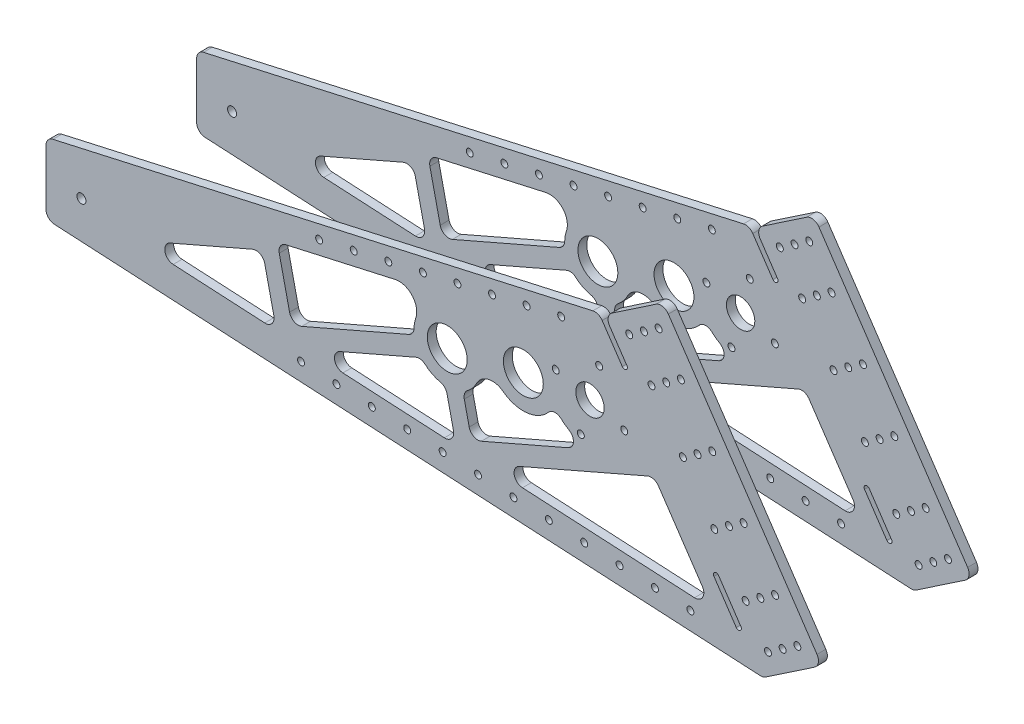
SolidWorks part; units mm, degrees
other "Markup1"
sketch "Sketch2"
sketch "Sketch9" plane through (0, 0, 0) normal (0, 0, 1) x (1, 0, 0)
sketch "Sketch12" plane through (116.0373, 167.646, 63.5) normal (0, 0, 1) x (1, 0, 0)
sketch "Sketch13" plane through (116.0373, 167.646, 63.5) normal (0, 0, 1) x (1, 0, 0)
sketch "Sketch14" plane through (116.0373, 167.646, 63.5) normal (0, 0, 1) x (1, 0, 0)
sketch "Sketch16" plane through (116.0373, 167.646, 63.5) normal (0, 0, 1) x (1, 0, 0)
sketch "Sketch17" plane through (116.0373, 167.8557, 63.5) normal (0, 0, 1) x (1, 0, 0)
sketch "Sketch18" plane through (116.0373, 167.7906, 57.15) normal (0, 0, 1) x (1, 0, 0)
sketch "Sketch19" plane through (84.5137, 127.089, 57.15) normal (0, 0, 1) x (1, 0, 0)
material "6061-T6 (SS)"
ref_plane "Front Plane" through (0, 0, 0) normal (0, 0, 1) x (1, 0, 0)
ref_plane "Top Plane" through (0, 0, 0) normal (0, 1, 0) x (1, 0, 0)
ref_plane "Right Plane" through (0, 0, 0) normal (1, 0, 0) x (0, 0, -1)
sketch "Grid" plane through (0, 0, 0) normal (0, 0, 1) x (1, 0, 0)
  line L0 (-23.2766, 0) -> (153.3593, 0) construction
  line L1 (0, 0) -> (0, 151.4205) construction
  line L6 (-1009.65, 1168.4) -> (-1009.65, 0) construction
  line L15 (-361.95, 520.7) -> (-803.275, 520.7)
  line L16 (-361.95, 520.7) -> (-361.95, 0)
  line L17 (-361.95, 0) -> (-803.275, 0)
  line L18 (-803.275, 520.7) -> (-803.275, 0)
  line L19 (-803.275, 0) -> (-1244.6, 0)
  line L20 (-803.275, 0) -> (-803.275, 825.5)
  line L21 (-803.275, 825.5) -> (-1244.6, 825.5)
  line L22 (-1244.6, 0) -> (-1244.6, 825.5)
  line L23 (-1030.732, 0) -> (-988.568, 0)
  line L24 (-1030.732, 0) -> (-1030.732, 1168.4)
  line L25 (-1030.732, 1168.4) -> (-988.568, 1168.4)
  line L26 (-988.568, 0) -> (-988.568, 1168.4)
  line L27 (-598.932, 0) -> (-556.768, 0)
  line L28 (-598.932, 0) -> (-598.932, 863.6)
  line L29 (-598.932, 863.6) -> (-556.768, 863.6)
  line L30 (-556.768, 0) -> (-556.768, 863.6)
  line L31 (-577.85, 863.6) -> (-577.85, 0) construction
  line L32 (-361.95, 520.7) -> (-361.95, 596.9) construction
  line L33 (-803.275, 825.5) -> (-803.275, 901.7) construction
  line L34 (-370.0766, 0) -> (-263.7141, 304.8)
  line L35 (-263.7141, 304.8) -> (-157.3516, 0)
  line L36 (-157.3516, 0) -> (-370.0766, 0)
  circle A0 centre (-100.3958, 159.9664) radius 120.65
  dimension "D3" = 241.3
  dimension "D2" = 76.2
  dimension "D4" = 304.8
  dimension "D5" = 212.725
  dimension "D7" = 42.164
  dimension "D8" = 520.7
  dimension "D9" = 304.8
  dimension "D10" = 1168.4
  dimension "D11" = 863.6
  dimension "D12" = 361.95
  dimension "D13" = 577.85
  dimension "D14" = 803.275
  dimension "D15" = 1009.65
sketch "ChassisXY" plane through (0, 0, 0) normal (0, 0, 1) x (1, 0, 0)
  line L0 (755.65, 93.726) -> (95.25, 93.726)
  line L1 (755.65, 93.726) -> (755.65, 42.926)
  line L2 (755.65, 42.926) -> (95.25, 42.926)
  line L3 (95.25, 93.726) -> (95.25, 42.926)
  line L15 (736.7108, 119.126) -> (675.4349, 119.126)
  line L16 (787.4, 42.926) -> (768.35, 42.926)
  line L19 (63.5, 169.926) -> (82.55, 169.926)
  line L20 (736.7108, 119.126) -> (694.5957, 90.719) construction
  line L21 (736.7108, 119.126) -> (717.55, 147.533) construction
  line L22 (694.5957, 90.719) -> (675.4349, 119.126) construction
  line L23 (717.55, 147.533) -> (675.4349, 119.126) construction
  line L27 (63.5, 169.926) -> (63.5, 42.926)
  line L31 (88.9, 42.926) -> (88.9, 1979.9925) construction
  line L32 (62.806, 1979.9925) -> (762, 1979.9925) construction
  line L33 (63.5, 42.926) -> (82.55, 42.926)
  line L36 (88.9, 1320.8) -> (762, 1320.8) construction
  line L37 (88.9, 988.6997) -> (131.0151, 1017.1067) construction
  line L45 (63.5, 42.926) -> (31.75, 42.926)
  line L46 (717.55, 147.533) -> (675.4349, 119.126) construction
  line L47 (717.55, 147.533) -> (-518.4596, 1979.9925) construction
  line L48 (675.4349, 119.126) -> (-560.5747, 1951.5855) construction
  line L49 (-518.4596, 1979.9925) -> (-560.5747, 1951.5855) construction
  line L50 (63.5, 42.926) -> (63.5, 169.926)
  line L51 (0, 74.676) -> (0, 138.176)
  line L52 (31.75, 169.926) -> (63.5, 169.926)
  line L54 (425.45, 93.726) -> (425.45, 42.926) construction
  line L55 (762, 42.926) -> (762, 1979.9925) construction
  line L56 (819.15, 169.926) -> (787.4, 169.926)
  line L57 (850.9, 74.676) -> (850.9, 138.176)
  line L58 (787.4, 42.926) -> (787.4, 169.926)
  line L59 (787.4, 42.926) -> (819.15, 42.926)
  line L60 (82.55, 169.926) -> (82.55, 42.926)
  line L61 (768.35, 169.926) -> (768.35, 42.926)
  line L62 (787.4, 169.926) -> (768.35, 169.926)
  line L63 (787.4, 169.926) -> (787.4, 42.926)
  line L64 (0, 0) -> (0, 200151.4205) construction
  line L65 (-200023.2766, 0) -> (200153.3593, 0) construction
  line L66 (95.25, 152.4) -> (755.65, 152.4) construction
  arc A5 (31.75, 169.926) -> (0, 138.176) centre (31.75, 138.176) ccw
  arc A6 (0, 74.676) -> (31.75, 42.926) centre (31.75, 74.676) ccw
  circle A7 centre (31.75, 74.676) radius 31.75 construction
  circle A8 centre (31.75, 138.176) radius 31.75 construction
  circle A9 centre (819.15, 138.176) radius 31.75 construction
  circle A10 centre (819.15, 74.676) radius 31.75 construction
  arc A11 (850.9, 74.676) -> (819.15, 42.926) centre (819.15, 74.676) cw
  arc A12 (819.15, 169.926) -> (850.9, 138.176) centre (819.15, 138.176) cw
  dimension "D3" = 63.5
  dimension "D1" = 50.8
  dimension "D2" = 56
  dimension "D4" = 38.1
  dimension "D5" = 50.8
  dimension "D6" = 12.7
  dimension "D7" = 19.05
  dimension "D8" = 42.926
  dimension "D9" = 109.474
  dimension "D10" = 25.4
  dimension "D12" = 660.4
  dimension "D13" = 6.35
ref_plane "Plane1" through (561.5696, 378.7835, 0) normal (0.829, 0.5592, 0) x (-0.5592, 0.829, 0)
sketch "carriage geo" plane through (0, 0, 0) normal (0, 0, 1) x (1, 0, 0)
  line L1 (116.0373, 195.326) -> (624.0373, 195.326)
  line L2 (116.0373, 195.326) -> (116.0373, 246.126)
  line L3 (116.0373, 246.126) -> (624.0373, 246.126)
  line L4 (624.0373, 195.326) -> (624.0373, 246.126)
  line L6 (624.0373, 195.326) -> (700.6322, 195.326) construction
  line L17 (717.55, 147.533) -> (-518.4596, 1979.9925) construction
  line L24 (624.0373, 246.126) -> (666.3671, 246.126) construction
  line L33 (666.3671, 246.126) -> (700.6322, 195.326) construction
  line L35 (675.4349, 119.126) -> (-560.5747, 1951.5855) construction
  line L64 (755.65, 93.726) -> (95.25, 93.726) construction
  circle A0 centre (154.1373, 220.726) radius 14.2875
  circle A58 centre (256.8816, 507.741) radius 25.4
  line B0 (120.4355, 364.2548) -> (144.4436, 355.656) construction
  line B1 (345.3934, 565.2279) -> (248.3868, 535.0242)
  line B2 (339.9907, 375.4447) -> (343.9447, 374.0285) construction
  line B3 (348.2442, 386.0326) -> (300.3235, 403.196) construction
  line B4 (308.577, 413.7839) -> (348.5895, 399.4529)
  line B5 (107.1432, 327.1426) -> (206.8255, 291.4401)
  line B6 (112.3162, 360.4178) -> (103.3062, 335.2619)
  line B7 (352.5436, 398.0367) -> (348.5895, 399.4529) construction
  line B8 (366.599, 439.1494) -> (341.413, 442.4393) construction
  line B9 (353.8882, 537.9448) -> (341.413, 442.4393) construction
  line B10 (343.9447, 374.0285) -> (352.5436, 398.0367)
  line B11 (348.5895, 399.4529) -> (308.577, 413.7839)
  line B12 (304.6229, 415.2001) -> (296.0241, 391.1919)
  line B13 (299.9781, 389.7757) -> (339.9907, 375.4447)
  line B14 (140.4752, 344.576) -> (141.8914, 348.5301) construction
  line B15 (129.3385, 325.9381) -> (133.2925, 324.5219) construction
  line B16 (110.7006, 337.0748) -> (109.2844, 333.1207) construction
  line B17 (121.8372, 355.7127) -> (117.8832, 357.1289) construction
  line B18 (117.8832, 357.1289) -> (110.7006, 337.0748)
  line B19 (109.2844, 333.1207) -> (129.3385, 325.9381)
  line B20 (141.8914, 348.5301) -> (121.8372, 355.7127)
  line B21 (133.2925, 324.5219) -> (140.4752, 344.576)
  line B22 (296.0241, 391.1919) -> (299.9781, 389.7757) construction
  line B23 (308.577, 413.7839) -> (304.6229, 415.2001) construction
  arc B24 (248.3868, 535.0242) -> (233.4586, 491.3735) centre (256.8816, 507.741) ccw
  circle B25 centre (256.8816, 507.741) radius 3.1877
  circle B26 centre (353.8882, 537.9448) radius 3.1877
  arc B27 (107.1432, 327.1426) -> (103.3062, 335.2619) centre (109.2844, 333.1207) cw
  circle B28 centre (341.413, 442.4393) radius 30 construction
  arc B29 (121.2422, 363.9009) -> (112.3162, 360.4178) centre (118.2943, 358.2767) ccw
  arc B30 (233.4586, 491.3735) -> (121.2422, 363.9009) centre (161.817, 441.3116) cw
  circle B31 centre (341.413, 442.4393) radius 25.4 construction
  circle B32 centre (366.599, 439.1494) radius 2.4892
  circle B33 centre (338.1231, 417.2533) radius 2.4892
  circle B34 centre (316.2269, 445.7292) radius 2.4892
  circle B35 centre (344.7029, 467.6254) radius 2.4892
  circle B36 centre (341.413, 442.4393) radius 10.16
  circle B37 centre (147.3899, 326.2177) radius 2.4892
  arc B38 (376.4624, 520.4251) -> (367.6342, 457.9958) centre (426.6271, 481.4924) ccw
  arc B39 (367.6342, 457.9958) -> (206.8255, 291.4401) centre (249.6484, 411.0026) cw
  arc B40 (133.2925, 324.5219) -> (129.3385, 325.9381) centre (131.3155, 325.23) cw
  arc B41 (343.9447, 374.0285) -> (339.9907, 375.4447) centre (341.9677, 374.7366) cw
  arc B42 (296.0241, 391.1919) -> (299.9781, 389.7757) centre (298.0011, 390.4838) ccw
  arc B43 (352.5436, 398.0367) -> (348.5895, 399.4529) centre (350.5666, 398.7448) ccw
  arc B44 (304.6229, 415.2001) -> (308.577, 413.7839) centre (306.5999, 414.492) cw
  arc B45 (109.2844, 333.1207) -> (110.7006, 337.0748) centre (109.9925, 335.0977) cw
  arc B46 (117.8832, 357.1289) -> (121.8372, 355.7127) centre (119.8602, 356.4208) cw
  arc B47 (141.8914, 348.5301) -> (140.4752, 344.576) centre (141.1833, 346.553) cw
  circle B48 centre (353.8882, 537.9448) radius 28.575
  line B49 (343.9447, 374.0285) -> (296.1197, 391.1577)
  line B50 (343.9447, 374.0285) -> (318.251, 302.291)
  line B51 (296.1197, 391.1577) -> (270.426, 319.4201)
  line B52 (318.251, 302.291) -> (270.426, 319.4201) construction
  line B53 (141.8571, 348.4344) -> (133.2925, 324.5219) construction
  line B54 (165.7696, 339.8698) -> (237.5071, 314.1761)
  line B55 (157.205, 315.9573) -> (228.9426, 290.2636)
  line B56 (237.5071, 314.1761) -> (228.9426, 290.2636) construction
  line B57 (161.4873, 327.9136) -> (233.2249, 302.2198) construction
  line B58 (165.7696, 339.8698) -> (157.205, 315.9573)
  line B59 (133.2925, 324.5219) -> (157.205, 315.9573) construction
  line B60 (141.8571, 348.4344) -> (165.7696, 339.8698) construction
  line B61 (308.4359, 312.5514) -> (331.9885, 378.3108) construction
  line B62 (320.0322, 382.5931) -> (294.3385, 310.8556) construction
  arc B63 (155.075, 274.6929) -> (165.7608, 168.0174) centre (154.1373, 220.726) ccw
  circle B64 centre (176.5553, 212.6967) radius 2.4892
  circle B65 centre (158.3928, 197.2968) radius 2.4892
  circle B66 centre (135.9748, 205.3261) radius 2.4892
  circle B67 centre (131.7194, 228.7553) radius 2.4892
  circle B68 centre (149.8819, 244.1552) radius 2.4892
  circle B69 centre (172.2999, 236.1259) radius 2.4892
  circle B70 centre (154.1373, 220.726) radius 23.8125 construction
  circle B71 centre (308.4359, 312.5514) radius 2.4892
  arc B72 (165.7608, 168.0174) -> (155.075, 274.6929) centre (154.1373, 220.726) ccw construction
  circle B73 centre (227.2467, 304.361) radius 2.4892
  circle B74 centre (284.5234, 321.116) radius 2.4892
  arc B75 (290.7123, 376.06) -> (193.2811, 330.0162) centre (218.9748, 401.7538) cw
  arc B76 (318.251, 302.291) -> (165.7608, 168.0174) centre (120.5341, 373.1059) cw
  circle B77 centre (312.7182, 324.5077) radius 2.4892
  circle B78 centre (288.8057, 333.0722) radius 2.4892
  circle B79 centre (317.0005, 336.4639) radius 2.4892
  circle B80 centre (293.088, 345.0285) radius 2.4892
  circle B81 centre (321.2828, 348.4202) radius 2.4892
  circle B82 centre (297.3703, 356.9847) radius 2.4892
  circle B83 centre (325.5651, 360.3764) radius 2.4892
  circle B84 centre (301.6526, 368.941) radius 2.4892
  circle B85 centre (329.8473, 372.3327) radius 2.4892
  circle B86 centre (305.9348, 380.8972) radius 2.4892
  arc B87 (162.2796, 314.1398) -> (155.075, 274.6929) centre (155.4279, 295.0098) cw
  circle B88 centre (215.2905, 308.6433) radius 2.4892
  circle B89 centre (203.3342, 312.9256) radius 2.4892
  circle B90 centre (191.378, 317.2079) radius 2.4892
  circle B91 centre (179.4217, 321.4901) radius 2.4892
  circle B92 centre (167.4655, 325.7724) radius 2.4892
  dimension "D2" = 28.575
  dimension "D3" = 25.4
  dimension "D4" = 38.1
  dimension "D8" = 101.6
  dimension "D5" = 50.8
  dimension "D1" = 50.8
  dimension "D6" = 12.7
  dimension "D7" = 508
sketch_block_instance "Block25-1"
sketch_block "Block25"
sketch_block_instance "Block26-1"
sketch_block "Block26"
sketch "carrriageyz" plane through (561.5696, 378.7835, 0) normal (0.829, 0.5592, 0) x (-0.5592, 0.829, 0)
  line L0 (-313.2035, 69.85) -> (769.957, 69.85) construction
  line L1 (769.957, -69.85) -> (-313.2035, -69.85) construction
  line L2 (-262.4035, 69.85) -> (-262.4035, -69.85) construction
  line L4 (-313.2035, 69.85) -> (-313.2035, -69.85) construction
  line L5 (-313.2035, 0) -> (-278.9385, 0) construction
  line L6 (769.957, 69.85) -> (769.957, -69.85) construction
  line L7 (-249.7114, 57.15) -> (-249.7114, 50.8)
  line L8 (-249.7114, 57.15) -> (-97.3114, 57.15)
  line L9 (-249.7114, 50.8) -> (-97.3114, 50.8)
  line L10 (-97.3114, 57.15) -> (-97.3114, 50.8)
  line L11 (106.8647, 0) -> (-106.8647, 0) construction
  line L12 (-97.3114, -57.15) -> (-97.3114, -50.8)
  line L13 (-249.7114, -50.8) -> (-97.3114, -50.8)
  line L14 (-249.7114, -57.15) -> (-97.3114, -57.15)
  line L15 (-249.7114, -57.15) -> (-249.7114, -50.8)
  line L16 (-218.5469, 31.75) -> (-148.6639, 31.75)
  line L17 (-174.4547, 57.15) -> (-206.8488, 57.15)
  line L19 (-221.2897, -57.15) -> (-160.0138, -57.15)
  line L21 (-219.5489, -57.15) -> (-127.4739, -57.15)
  line L22 (-219.5489, 63.5) -> (-127.4739, 63.5)
  line L23 (-219.5489, 63.5) -> (-219.5489, 57.15)
  line L24 (-219.5489, 57.15) -> (-127.4739, 57.15)
  line L25 (-127.4739, 63.5) -> (-127.4739, 57.15)
  line L26 (-127.4739, -63.5) -> (-127.4739, -57.15)
  line L27 (-219.5489, -63.5) -> (-127.4739, -63.5)
  line L28 (-219.5489, -63.5) -> (-219.5489, -57.15)
  line L29 (-218.5469, 31.75) -> (-218.5469, -31.75)
  line L30 (-218.5469, -31.75) -> (-148.6639, -31.75)
  line L31 (-148.6639, 31.75) -> (-148.6639, -31.75)
  line L33 (-97.3114, -69.1134) -> (-125.8864, -69.1134)
  line L34 (-97.3114, 57.15) -> (-125.8864, 57.15)
  line L35 (-97.3114, 57.15) -> (-97.3114, 69.1134)
  line L36 (-97.3114, 69.1134) -> (-125.8864, 69.1134)
  line L37 (-125.8864, 57.15) -> (-125.8864, 69.1134)
  line L38 (-249.7114, 57.15) -> (-221.1364, 57.15)
  line L39 (-249.7114, 57.15) -> (-249.7114, 69.1134)
  line L40 (-249.7114, 69.1134) -> (-221.1364, 69.1134)
  line L41 (-221.1364, 57.15) -> (-221.1364, 69.1134)
  line L42 (-125.8864, -57.15) -> (-125.8864, -69.1134)
  line L43 (-97.3114, -57.15) -> (-125.8864, -57.15)
  line L44 (-97.3114, -57.15) -> (-97.3114, -69.1134)
  line L45 (-249.7114, -69.1134) -> (-221.1364, -69.1134)
  line L46 (-221.1364, -57.15) -> (-221.1364, -69.1134)
  line L47 (-249.7114, -57.15) -> (-221.1364, -57.15)
  line L48 (-249.7114, -57.15) -> (-249.7114, -69.1134)
  line L49 (-111.5989, 69.1134) -> (-111.5989, -69.1134) construction
  line L50 (-235.4239, 69.1134) -> (-235.4239, -69.1134) construction
  point P4 (-313.2035, 0)
  point P31 (-148.6639, 0)
  point P41 (-190.6518, 57.15)
  point P53 (-111.5989, 0)
  dimension "D1" = 139.7
  dimension "D2" = 12.7
  dimension "D3" = 6.35
  dimension "D4" = 63.5
  dimension "D5" = 6.35
  dimension "D6" = 152.4
  dimension "D7" = 28.575
  dimension "D8" = 11.9634
  dimension "D9" = 50.8
  dimension "D10" = 1.5875
  dimension "D11" = 1.5875
ref_plane "bearing block interface plane" through (0, 0, 57.15) normal (0, 0, 1) x (1, 0, 0)
sketch "bearing block interface plate" plane through (0, 0, 57.15) normal (0, 0, 1) x (1, 0, 0)
  line L0 (529.0514, 336.1484) -> (571.1665, 364.5554)
  line L1 (529.0514, 336.1484) -> (642.6794, 167.688)
  line L2 (571.1665, 364.5554) -> (684.7945, 196.095)
  line L3 (642.6794, 167.688) -> (684.7945, 196.095)
  line L4 (675.4349, 119.126) -> (-560.5747, 1951.5855) construction
  line L5 (717.55, 147.533) -> (-518.4596, 1979.9925) construction
  line L6 (635.5777, 178.2167) -> (677.6928, 206.6237) construction
  line L7 (585.8654, 251.9182) -> (627.9805, 280.3252) construction
  line L10 (545.0304, 312.4586) -> (587.1455, 340.8656) construction
  line L12 (528.3092, 320.3288) -> (546.682, 332.7214) construction
  line L15 (606.2073, 289.894) -> (628.6962, 256.5529) construction
  line L16 (522.4272, 322.7212) -> (526.7202, 333.2764) construction
  line L17 (529.0514, 336.1484) -> (536.1532, 325.6196) construction
  line L18 (527.0768, 314.0996) -> (540.247, 311.4938) construction
  line L21 (577.876, 263.7631) -> (619.9911, 292.1701) construction
  line L22 (626.7005, 191.3777) -> (668.8156, 219.7847) construction
  line L23 (611.7695, 190.2657) -> (623.1643, 190.2921) construction
  line L24 (610.7216, 215.0675) -> (652.8367, 243.4745) construction
  line L25 (605.5175, 197.8065) -> (608.0351, 210.9939) construction
  line L26 (611.7548, 196.6157) -> (630.1275, 209.0082) construction
  circle A0 centre (646.1065, 185.3185) radius 2.4892
  circle A1 centre (656.6352, 192.4202) radius 2.4892
  circle A2 centre (667.164, 199.522) radius 2.4892
  circle A3 centre (567.7395, 346.9249) radius 2.4892
  circle A4 centre (557.2107, 339.8231) radius 2.4892
  circle A5 centre (546.682, 332.7214) radius 2.4892
  arc A7 (522.4272, 322.7212) -> (527.0768, 314.0996) centre (528.3092, 320.3288) ccw construction
  circle A12 centre (562.6609, 309.0316) radius 2.4892
  circle A13 centre (573.1897, 316.1334) radius 2.4892
  circle A14 centre (583.7185, 323.2351) radius 2.4892
  circle A15 centre (606.2073, 289.894) radius 2.4892
  circle A16 centre (595.6786, 282.7922) radius 2.4892
  circle A17 centre (585.1498, 275.6905) radius 2.4892
  circle A18 centre (628.6962, 256.5529) radius 2.4892
  circle A19 centre (618.1674, 249.4511) radius 2.4892
  circle A20 centre (607.6387, 242.3494) radius 2.4892
  circle A21 centre (651.1851, 223.2117) radius 2.4892
  circle A22 centre (640.6563, 216.11) radius 2.4892
  circle A23 centre (630.1275, 209.0082) radius 2.4892
  arc A24 (526.7202, 333.2764) -> (529.0514, 336.1484) centre (532.6023, 330.884) cw construction
  arc A25 (540.247, 311.4938) -> (545.0304, 312.4586) centre (541.4795, 317.723) ccw construction
  arc A29 (623.1643, 190.2921) -> (626.7005, 191.3777) centre (623.1496, 196.6421) ccw construction
  arc A30 (611.7695, 190.2657) -> (605.5175, 197.8065) centre (611.7548, 196.6157) cw construction
  arc A31 (608.0351, 210.9939) -> (610.7216, 215.0675) centre (614.2724, 209.8031) cw construction
  point P28 (617.4518, 273.2234)
  dimension "D3" = 4.9784
  dimension "D8" = 12.7
  dimension "D10" = 2
  dimension "D13" = 6.35
  dimension "D1" = 12.7
  dimension "D2" = 12.7
  dimension "D4" = 12.7
  dimension "D5" = 28.575
  dimension "D6" = 203.2
  dimension "D7" = 33.3375
  dimension "D9" = 9.4615
  dimension "D11" = 4
  dimension "D12" = 12.7
extrude "Boss-Extrude1" add sketch "bearing block interface plate" against normal blind 6.35
fillet "Fillet2" radius 6.35 4 edges at (642.6794, 167.688, 53.975) (571.1665, 364.5554, 53.975) (529.0514, 336.1484, 53.975) (684.7945, 196.095, 53.975)
ref_plane "carriage support plane" through (0, 0, 57.15) normal (0, 0, 1) x (1, 0, 0)
sketch "plate+gb" plane through (0, 0, 57.15) normal (0, 0, 1) x (1, 0, 0)
  line L1 (717.55, 147.533) -> (-518.4596, 1979.9925) construction
  line L3 (116.0373, 195.326) -> (624.0373, 195.326) construction
  line L4 (128.7373, 195.326) -> (642.6794, 167.688)
  line L8 (532.6023, 330.884) -> (639.1286, 172.9523) construction
  line L10 (116.0373, 246.126) -> (624.0373, 246.126) construction
  line L11 (128.7373, 246.126) -> (128.7373, 195.326)
  line L12 (116.0373, 195.326) -> (116.0373, 246.126) construction
  line L13 (571.1665, 364.5554) -> (529.0514, 336.1484)
  line L17 (526.5201, 336.3247) -> (543.3723, 311.3403) construction
  line L18 (528.1782, 337.4431) -> (545.0304, 312.4586)
  line L19 (416.2866, 258.7212) -> (154.1373, 220.726) construction
  line L20 (416.2683, 274.9957) -> (154.0767, 274.701) construction
  line L21 (420.8895, 243.1112) -> (169.4032, 168.9548) construction
  line L22 (518.57, 277.876) -> (525.144, 302.4105) construction
  line L24 (529.0514, 336.1484) -> (128.7373, 246.126)
  line L26 (256.3165, 274.8159) -> (529.0514, 336.1484) construction
  line L30 (524.862, 335.2063) -> (541.7142, 310.2219)
  line L31 (529.0514, 336.1484) -> (642.6794, 167.688) construction
  line L38 (642.6794, 167.688) -> (684.7945, 196.095) construction
  line L39 (642.6794, 167.688) -> (684.7945, 196.095)
  line L40 (545.0304, 312.4586) -> (587.1455, 340.8656) construction
  line L43 (609.0635, 213.9491) -> (625.0424, 190.2593) construction
  line L44 (610.7216, 215.0675) -> (626.7005, 191.3777)
  line L45 (607.4054, 212.8307) -> (623.3843, 189.1409)
  line L59 (684.7945, 196.095) -> (571.1665, 364.5554)
  circle A0 centre (470.8051, 270.9813) radius 14.2875
  circle A1 centre (416.2866, 258.7212) radius 14.2875
  arc A2 (155.075, 274.6929) -> (165.7608, 168.0174) centre (154.1373, 220.726) ccw construction
  arc A4 (165.7608, 168.0174) -> (155.075, 274.6929) centre (154.1373, 220.726) ccw construction
  circle A5 centre (518.57, 277.876) radius 10.16
  circle A12 centre (518.57, 277.876) radius 25.4 construction
  circle A13 centre (518.57, 277.876) radius 7.62 construction
  circle A14 centre (470.8051, 270.9813) radius 40.64 construction
  circle A15 centre (470.8051, 270.9813) radius 15.24 construction
  circle A16 centre (416.2866, 258.7212) radius 40.64 construction
  circle A17 centre (416.2866, 258.7212) radius 16.2745 construction
  circle A18 centre (525.144, 302.4105) radius 2.4892
  circle A19 centre (543.1045, 271.302) radius 2.4892
  circle A20 centre (511.996, 253.3415) radius 2.4892
  circle A21 centre (494.0355, 284.45) radius 2.4892
  arc A22 (528.1782, 337.4431) -> (524.862, 335.2063) centre (526.5201, 336.3247) ccw
  arc A23 (541.7142, 310.2219) -> (545.0304, 312.4586) centre (543.3723, 311.3403) ccw
  arc A24 (610.7216, 215.0675) -> (607.4054, 212.8307) centre (609.0635, 213.9491) ccw
  circle A25 centre (607.6387, 242.3494) radius 2.4892 construction
  circle A26 centre (618.1674, 249.4511) radius 2.4892 construction
  circle A27 centre (628.6962, 256.5529) radius 2.4892 construction
  circle A28 centre (606.2073, 289.894) radius 2.4892 construction
  circle A29 centre (595.6786, 282.7922) radius 2.4892 construction
  circle A30 centre (585.1498, 275.6905) radius 2.4892 construction
  circle A31 centre (562.6609, 309.0316) radius 2.4892 construction
  circle A32 centre (573.1897, 316.1334) radius 2.4892 construction
  circle A33 centre (583.7185, 323.2351) radius 2.4892 construction
  circle A35 centre (518.57, 277.876) radius 30 construction
  circle A41 centre (607.6387, 242.3494) radius 2.4892
  circle A42 centre (618.1674, 249.4511) radius 2.4892
  circle A43 centre (628.6962, 256.5529) radius 2.4892
  circle A44 centre (606.2073, 289.894) radius 2.4892
  circle A45 centre (595.6786, 282.7922) radius 2.4892
  circle A46 centre (585.1498, 275.6905) radius 2.4892
  circle A47 centre (562.6609, 309.0316) radius 2.4892
  circle A48 centre (573.1897, 316.1334) radius 2.4892
  circle A49 centre (583.7185, 323.2351) radius 2.4892
  arc A59 (623.3843, 189.1409) -> (626.7005, 191.3777) centre (625.0424, 190.2593) ccw
  circle A63 centre (567.7395, 346.9249) radius 2.4892 construction
  circle A68 centre (557.2107, 339.8231) radius 2.4892 construction
  circle A74 centre (546.682, 332.7214) radius 2.4892 construction
  circle A75 centre (651.1851, 223.2117) radius 2.4892 construction
  circle A77 centre (640.6563, 216.11) radius 2.4892 construction
  circle A78 centre (630.1275, 209.0082) radius 2.4892 construction
  circle A79 centre (567.7395, 346.9249) radius 2.4892
  circle A80 centre (557.2107, 339.8231) radius 2.4892
  circle A81 centre (546.682, 332.7214) radius 2.4892
  circle A82 centre (651.1851, 223.2117) radius 2.4892
  circle A83 centre (640.6563, 216.11) radius 2.4892
  circle A84 centre (630.1275, 209.0082) radius 2.4892
  circle A85 centre (646.1065, 185.3185) radius 2.4892 construction
  circle A86 centre (656.6352, 192.4202) radius 2.4892 construction
  circle A87 centre (667.164, 199.522) radius 2.4892 construction
  circle A91 centre (646.1065, 185.3185) radius 2.4892
  circle A93 centre (656.6352, 192.4202) radius 2.4892
  circle A94 centre (667.164, 199.522) radius 2.4892
  point P10 (534.9462, 323.8325)
  point P47 (617.053, 202.1042)
  point P64 (518.57, 277.876)
  dimension "D2" = 50.8
  dimension "D15" = 28.575
  dimension "D16" = 20.32
  dimension "D18" = 4.9784
  dimension "D19" = 15
  dimension "D20" = 31.75
  dimension "D11" = 4
  dimension "D8" = 41.275
  dimension "D9" = 50.8
  dimension "D10" = 50.8
  dimension "D12" = 12.7
  dimension "D17" = 4
extrude "Boss-Extrude2" add sketch "plate+gb" against normal blind 6.35 contours L13 L11 L4 A49 A48 A47 A46 A45 A44 A43 A42 A41 A94 A93 A91 A21 A20 A19 A18 A5 A1 region at (431.8967, 241.8923, 57.15)
fillet "Fillet1" radius 6.35 7 edges at (128.7373, 195.326, 53.975) (128.7373, 246.126, 53.975) (571.1665, 364.5554, 53.975) (642.6794, 167.688, 53.975) (684.7945, 196.095, 53.975) (529.0514, 336.1484, 53.975) (524.862, 335.2063, 53.975)
sketch "tube" plane through (0, 0, 57.15) normal (0, 0, 1) x (1, 0, 0)
  line L7 (522.7198, 324.9617) -> (135.7839, 237.9478)
  line L11 (135.4283, 207.6845) -> (641.235, 180.484)
  line L12 (135.4283, 207.6845) -> (641.235, 180.484) construction
  line L13 (522.7198, 324.9617) -> (135.7839, 237.9478) construction
  circle A41 centre (154.1373, 220.726) radius 3.2639
  circle A48 centre (497.9387, 319.3889) radius 2.4892
  circle A49 centre (473.1576, 313.8161) radius 2.4892
  circle A50 centre (448.3764, 308.2434) radius 2.4892
  circle A51 centre (423.5953, 302.6706) radius 2.4892
  circle A52 centre (398.8142, 297.0978) radius 2.4892
  circle A53 centre (374.0331, 291.5251) radius 2.4892
  circle A54 centre (590.5083, 183.2119) radius 2.4892
  circle A55 centre (565.1449, 184.5758) radius 2.4892
  circle A56 centre (539.7816, 185.9398) radius 2.4892
  circle A57 centre (514.4182, 187.3038) radius 2.4892
  circle A58 centre (489.0549, 188.6677) radius 2.4892
  circle A59 centre (463.6915, 190.0317) radius 2.4892
  circle A60 centre (438.3282, 191.3956) radius 2.4892
  circle A61 centre (412.9648, 192.7596) radius 2.4892
  circle A62 centre (387.6015, 194.1235) radius 2.4892
  circle A63 centre (362.2381, 195.4875) radius 2.4892
  circle A64 centre (336.8748, 196.8514) radius 2.4892
  circle A65 centre (311.5114, 198.2154) radius 2.4892
  circle A70 centre (349.2519, 285.9523) radius 2.4892
  circle A71 centre (324.4708, 280.3796) radius 2.4892
  dimension "D3" = 12.7
  dimension "D14" = 6.5278
  dimension "D4" = 4.9784
  dimension "D5" = 50.8
  dimension "D15" = 25.4
  dimension "D7" = 12
  dimension "D11" = 9.525
  dimension "D16" = 25.4
  dimension "D6" = 25.4
extrude "Cut-Extrude1" cut sketch "tube" against normal up to next
sketch "Sketch20" plane through (0, 0, 57.15) normal (0, 0, 1) x (1, 0, 0)
  line L0 (178.8573, 214.8878) -> (288.2885, 262.48) construction
  line L1 (288.2885, 262.48) -> (300.4616, 208.3484) construction
  line L2 (300.4616, 208.3484) -> (416.2866, 258.7212) construction
  line L3 (416.2866, 258.7212) -> (429.1709, 201.4268) construction
  line L4 (429.1709, 201.4268) -> (561.0825, 258.7959) construction
  line L5 (181.3898, 209.0647) -> (283.7782, 253.5939)
  line L6 (283.7782, 253.5939) -> (295.9513, 199.4623)
  line L7 (295.9513, 199.4623) -> (411.7763, 249.8352)
  line L8 (173.8491, 236.745) -> (522.9963, 315.261)
  line L9 (522.9963, 315.261) -> (606.1998, 191.9068)
  line L10 (606.1998, 191.9068) -> (178.8573, 214.8878)
  line L11 (134.7464, 195.0029) -> (640.553, 167.8023) construction
  line L12 (520.63, 334.2546) -> (133.6942, 247.2407) construction
  line L13 (527.2876, 331.6102) -> (541.7142, 310.2219) construction
  line L14 (128.7373, 241.0454) -> (128.7373, 201.3437) construction
  line L15 (411.7763, 249.8352) -> (424.6606, 192.5407)
  line L16 (424.6606, 192.5407) -> (564.6938, 253.4419)
  line L17 (176.3248, 220.711) -> (292.7988, 271.3661)
  line L18 (292.7988, 271.3661) -> (304.9719, 217.2345)
  line L19 (304.9719, 217.2345) -> (420.7969, 267.6073)
  line L20 (420.7969, 267.6073) -> (433.6812, 210.3129)
  line L21 (433.6812, 210.3129) -> (558.55, 264.619)
  line L22 (424.6606, 192.5407) -> (563.6151, 252.9727) construction
  arc A0 (378.9306, 282.8636) -> (393.7412, 266.3854) centre (381.717, 270.473) cw
  arc A1 (492.8846, 262.0635) -> (548.723, 277.1196) centre (518.57, 277.876) ccw
  circle A2 centre (518.57, 277.876) radius 10.16 construction
  circle A3 centre (511.996, 253.3415) radius 4.7625 construction
  circle A8 centre (154.1373, 220.726) radius 25.4
  circle A9 centre (416.2866, 258.7212) radius 23.8125
  circle A10 centre (470.8051, 270.9813) radius 23.8125
  circle A12 centre (416.2866, 258.7212) radius 14.2875 construction
  arc A13 (430.701, 277.6754) -> (449.6639, 281.9398) centre (438.3887, 287.7843) ccw
  arc A14 (437.4277, 247.7628) -> (456.3907, 252.0272) centre (448.703, 241.9183) cw
  point P39 (563.5413, 255.1506)
  dimension "D4" = 9.525
  dimension "D5" = 12.7
  dimension "D6" = 9.525
  dimension "D1" = 22.225
  dimension "D2" = 19.05
  dimension "D3" = 12.7
  dimension "D7" = 6.35
  dimension "D8" = 6.35
extrude "Cut-Extrude2" cut sketch "Sketch20" against normal up to next contours L10 L6 L5 | A9 A0 L8 L18 L19 | A9 L7 L10 L15 | A14 A9 L20 L21 A1 A10 | L16 L10 L9 region at (256.8929, 225.4741, 57.15) region at (381.5439, 218.4291, 57.15) region at (342.1598, 254.4584, 57.15) region at (538.0781, 215.3378, 57.15) region at (463.244, 237.3713, 57.15)
fillet "Fillet3" radius 6.35 17 edges at (392.7081, 255.3914, 53.975) (304.9719, 217.2345, 53.975) (294.4838, 263.8732, 53.975) (492.8846, 262.0635, 53.975) (519.7296, 247.7358, 53.975) (433.6812, 210.3129, 53.975) (427.5171, 237.7234, 53.975) (564.6938, 253.4419, 53.975) (606.1998, 191.9068, 53.975) (443.3407, 200.6648, 53.975) (415.1266, 234.937, 53.975) (422.5827, 201.7811, 53.975) (314.6314, 207.5864, 53.975) (397.7731, 243.7451, 53.975) (283.7782, 253.5939, 53.975) (293.8733, 208.7027, 53.975) (193.0271, 214.1258, 53.975)
mirror "Mirror1" about plane through (0, 0, 0) normal (0, 0, 1) of bodies 115 105 104 101
equation "\"D3@plate+gb\" = 12 / 20"
equation "\"D4@plate+gb\" = 64 / 20"
equation "\"D5@plate+gb\" = 24 / 20"
equation "\"D6@plate+gb\" = 64 / 20"
equation "\"D7@plate+gb\" = 0.25 /  ( sin ( 180 / 16 )  ) "
equation "\"D22@plate+gb\"=60mm"
